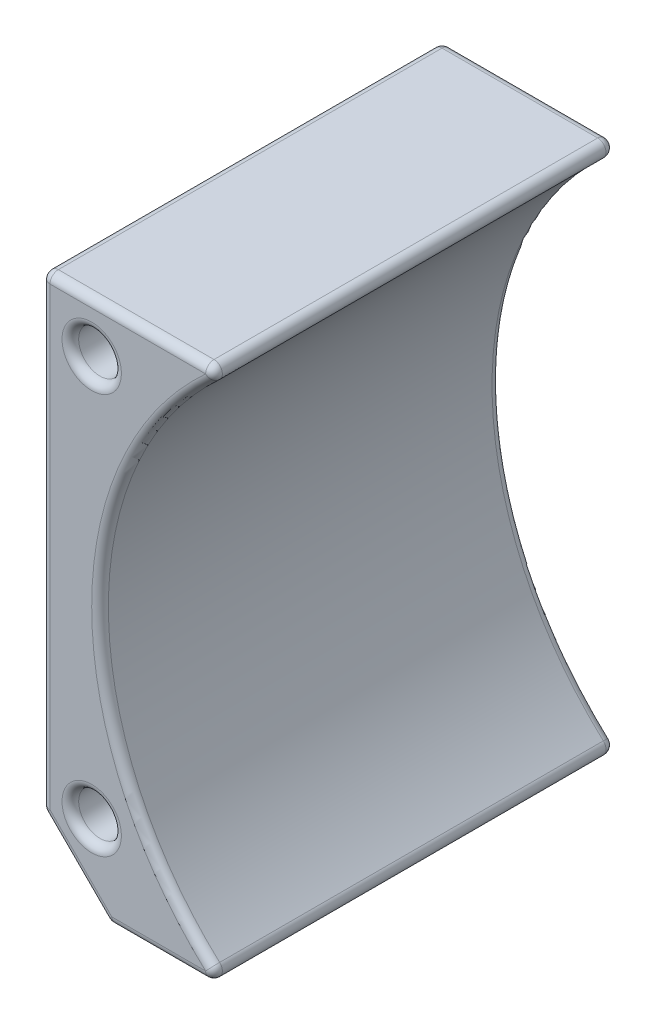
SolidWorks part; units mm, degrees
ref_plane "Front Plane" through (0, 0, 0) normal (0, 0, 1) x (1, 0, 0)
ref_plane "Top Plane" through (0, 0, 0) normal (0, 1, 0) x (1, 0, 0)
ref_plane "Right Plane" through (0, 0, 0) normal (1, 0, 0) x (0, 0, -1)
sketch "Sketch1" plane through (0, 0, 0) normal (0, 0, 1) x (1, 0, 0)
  line L1 (0, 0) -> (17.7546, 0)
  line L2 (0, 0) -> (0, 50.8)
  line L3 (0, 50.8) -> (17.7546, 50.8)
  arc A0 (17.7546, 50.8) -> (17.7546, 0) centre (38.1, 25.4) ccw
  point P7 (17.7875, -0.0264)
  dimension "D4" = 65.0875
  dimension "D1" = 50.8
  dimension "D2" = 25.4
  dimension "D3" = 38.1
extrude "Boss-Extrude1" add sketch "Sketch1" along normal blind 38.1
sketch "Sketch2" plane through (0, 0, 38.1) normal (0, 0, 1) x (1, 0, 0)
  line L0 (17.7546, 50.8) -> (0, 50.8) construction
  line L1 (0, 50.8) -> (0, 0) construction
  line L2 (0, 0) -> (17.7546, 0) construction
  circle A0 centre (4.7625, 46.0375) radius 2.032
  circle A1 centre (4.7625, 7.9375) radius 2.032
  point P10 (0, 0)
  point P11 (0, 0)
  point P12 (0, 0)
  point P13 (0, 0)
  point P14 (0, 0)
  dimension "D4" = 4.064
  dimension "D1" = 4.7625
  dimension "D2" = 4.7625
  dimension "D3" = 7.9375
extrude "Cut-Extrude1" cut sketch "Sketch2" against normal through all
chamfer "Chamfer1" distance 6.35 angle 45 1 edges at (0, 0, 19.05)
fillet "Fillet1" radius 0.7937 19 edges at (3.175, 3.175, 38.1) (0, 6.35, 19.05) (3.175, 3.175, 0) (6.35, 0, 19.05) (17.7546, 0, 19.05) (17.7546, 50.8, 19.05) (0, 50.8, 19.05) (8.8773, 50.8, 38.1) (5.5563, 25.4, 38.1) (12.0523, 0, 38.1) (0, 28.575, 38.1) (8.8773, 50.8, 0) (5.5563, 25.4, 0) (12.0523, 0, 0) (0, 28.575, 0) (6.7945, 46.0375, 0) (6.7945, 46.0375, 38.1) (6.7945, 7.9375, 38.1) (6.7945, 7.9375, 0)
